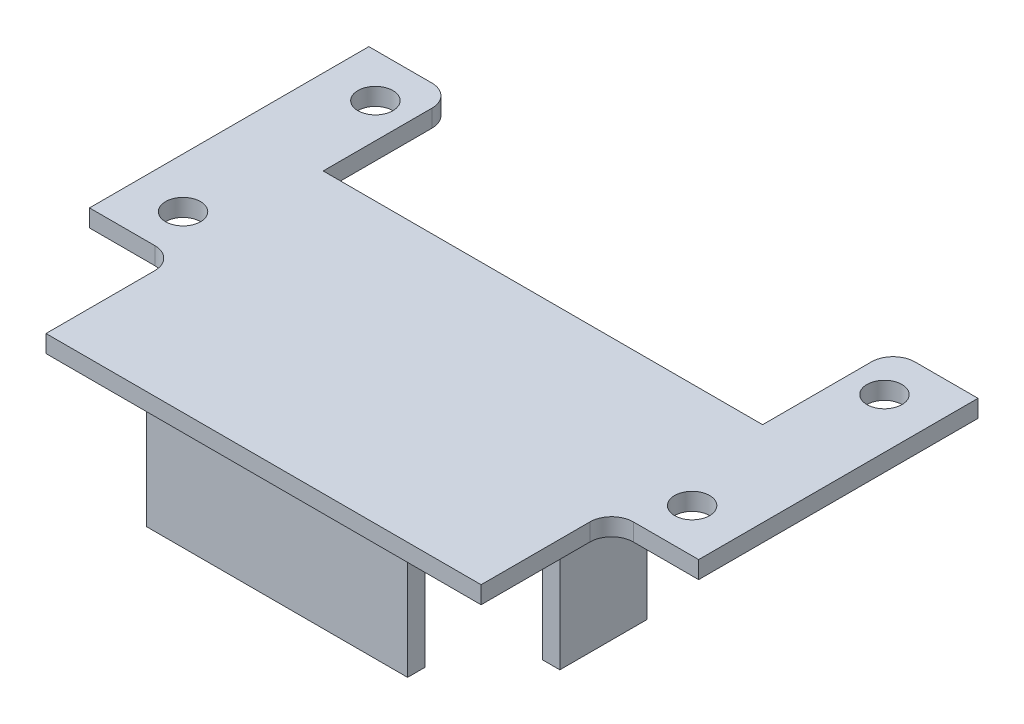
SolidWorks part; units mm, degrees
ref_plane "Front Plane" through (0, 0, 0) normal (0, 0, 1) x (1, 0, 0)
ref_plane "Top Plane" through (0, 0, 0) normal (0, 1, 0) x (1, 0, 0)
ref_plane "Right Plane" through (0, 0, 0) normal (1, 0, 0) x (0, 0, -1)
sketch "Sketch1" plane through (0, 0, 0) normal (0, 1, 0) x (1, 0, 0)
  line L0 (0, 0) -> (0, 20.3835) construction
  line L1 (44.45, -20.3835) -> (-44.45, -20.3835)
  line L2 (44.45, -20.3835) -> (44.45, 20.3835)
  line L3 (44.45, 20.3835) -> (-44.45, 20.3835) construction
  line L4 (-44.45, -20.3835) -> (-44.45, 20.3835)
  line L5 (44.45, -20.3835) -> (-44.45, 20.3835) construction
  line L6 (44.45, 20.3835) -> (-44.45, -20.3835) construction
  line L7 (0, 0) -> (44.45, 0) construction
  line L13 (-32.0675, 17.2085) -> (-32.0675, 1.3335)
  line L14 (-44.45, 20.3835) -> (-35.2425, 20.3835)
  line L15 (-32.0675, 1.3335) -> (32.0675, 1.3335)
  line L16 (32.0675, 17.2085) -> (32.0675, 1.3335)
  line L17 (44.45, 20.3835) -> (35.2425, 20.3835)
  circle A0 centre (37.1475, -14.0335) radius 2.5527
  circle A2 centre (37.1475, 14.0335) radius 2.5527
  circle A3 centre (-37.1475, -14.0335) radius 2.5527
  circle A4 centre (-37.1475, 14.0335) radius 2.5527
  arc A7 (-32.0675, 17.2085) -> (-35.2425, 20.3835) centre (-35.2425, 17.2085) ccw
  arc A8 (32.0675, 17.2085) -> (35.2425, 20.3835) centre (35.2425, 17.2085) cw
  point P0 (0, 0)
  point P19 (0, 1.3335)
  point P23 (-32.0675, 20.3835)
  point P30 (32.0675, 20.3835)
  dimension "D3" = 5.1054
  dimension "D6" = 28.067
  dimension "D7" = 5.1054
  dimension "D10" = 5.08
  dimension "D12" = 3.175
  dimension "D1" = 6.35
  dimension "D2" = 88.9
  dimension "D4" = 6.35
  dimension "D5" = 7.3025
  dimension "D8" = 7.3025
  dimension "D11" = 19.05
extrude "Boss-Extrude1" add sketch "Sketch1" along normal blind 2.54
sketch "Sketch7" plane through (0, 2.54, 0) normal (0, 1, 0) x (1, 0, 0)
  line L1 (-44.45, -20.3835) -> (44.45, -20.3835)
  line L2 (-44.45, -20.3835) -> (-44.45, -39.4335)
  line L3 (-44.45, -39.4335) -> (44.45, -39.4335)
  line L4 (44.45, -20.3835) -> (44.45, -39.4335)
  dimension "D1" = 19.05
extrude "Boss-Extrude2" add sketch "Sketch7" against normal up to surface (2.54 mm away) up to face at (0, 0, -7.9166)
sketch "Sketch6" plane through (0, 0, 0) normal (0, -1, 0) x (-1, 0, 0)
  line L0 (0, 1.3335) -> (0, -39.4335) construction
  line L5 (-32.0675, 1.3335) -> (32.0675, 1.3335) construction
  line L11 (-44.45, -39.4335) -> (44.45, -39.4335) construction
  line L26 (25.4, -33.655) -> (-25.4, -33.655) construction
  line L27 (25.4, -33.655) -> (25.4, -4.445) construction
  line L28 (25.4, -4.445) -> (-25.4, -4.445) construction
  line L29 (-25.4, -33.655) -> (-25.4, -4.445) construction
  line L30 (25.4, -33.655) -> (-25.4, -4.445) construction
  line L31 (25.4, -4.445) -> (-25.4, -33.655) construction
  line L32 (0, -19.05) -> (44.45, -19.05) construction
  line L33 (44.45, 20.3835) -> (44.45, -39.4335) construction
  line L34 (-19.05, -34.925) -> (-19.05, -37.465)
  line L35 (26.67, -34.925) -> (-26.67, -34.925) construction
  line L36 (26.67, -34.925) -> (26.67, -3.175) construction
  line L37 (26.67, -3.175) -> (-26.67, -3.175) construction
  line L38 (-26.67, -34.925) -> (-26.67, -3.175) construction
  line L39 (26.67, -34.925) -> (-26.67, -3.175) construction
  line L40 (26.67, -3.175) -> (-26.67, -34.925) construction
  line L41 (-19.05, -34.925) -> (19.05, -34.925)
  line L42 (0, -34.925) -> (0, -37.465) construction
  line L43 (-19.05, -37.465) -> (19.05, -37.465)
  line L44 (19.05, -34.925) -> (19.05, -37.465)
  line L45 (-19.05, -3.175) -> (-19.05, -0.635)
  line L46 (-19.05, -3.175) -> (19.05, -3.175)
  line L47 (0, -3.175) -> (0, -0.635) construction
  line L48 (-19.05, -0.635) -> (19.05, -0.635)
  line L49 (19.05, -3.175) -> (19.05, -0.635)
  line L50 (26.67, -25.4) -> (29.21, -25.4)
  line L51 (26.67, -19.05) -> (29.21, -19.05) construction
  line L52 (26.67, -25.4) -> (26.67, -12.7)
  line L53 (26.67, -12.7) -> (29.21, -12.7)
  line L54 (29.21, -25.4) -> (29.21, -12.7)
  line L55 (-26.67, -25.4) -> (-26.67, -12.7)
  line L56 (-26.67, -12.7) -> (-29.21, -12.7)
  line L57 (-29.21, -25.4) -> (-29.21, -12.7)
  line L58 (-26.67, -25.4) -> (-29.21, -25.4)
  point P14 (0, -19.05)
  point P29 (19.05, -1.905)
  point P30 (-19.05, -1.905)
  dimension "D1" = 29.21
  dimension "D2" = 50.8
  dimension "D3" = 1.27
  dimension "D4" = 1.27
  dimension "D5" = 19.05
  dimension "D6" = 2.54
  dimension "D7" = 19.05
  dimension "D8" = 2.54
  dimension "D9" = 2.54
  dimension "D10" = 6.35
extrude "Boss-Extrude3" add sketch "Sketch6" along normal blind 16.51
sketch "Sketch8" plane through (0, 0, 0) normal (0, -1, 0) x (1, 0, 0)
  line L0 (0, 39.4335) -> (0, -1.3335) construction
  line L1 (-44.45, 39.4335) -> (-31.75, 39.4335)
  line L2 (-44.45, 39.4335) -> (-44.45, 20.3835)
  line L3 (-44.45, 20.3835) -> (-34.925, 20.3835)
  line L4 (-31.75, 39.4335) -> (-31.75, 23.5585)
  line L5 (44.45, 39.4335) -> (-44.45, 39.4335) construction
  line L6 (32.0675, -1.3335) -> (-32.0675, -1.3335) construction
  line L7 (44.45, 20.3835) -> (34.925, 20.3835)
  line L8 (31.75, 39.4335) -> (31.75, 23.5585)
  line L9 (44.45, 39.4335) -> (31.75, 39.4335)
  line L10 (44.45, 39.4335) -> (44.45, 20.3835)
  arc A0 (-34.925, 20.3835) -> (-31.75, 23.5585) centre (-34.925, 23.5585) ccw
  arc A1 (34.925, 20.3835) -> (31.75, 23.5585) centre (34.925, 23.5585) cw
  point P13 (-31.75, 20.3835)
  dimension "D3" = 3.175
  dimension "D1" = 12.7
  dimension "D2" = 19.05
extrude "Cut-Extrude1" cut sketch "Sketch8" against normal through all
